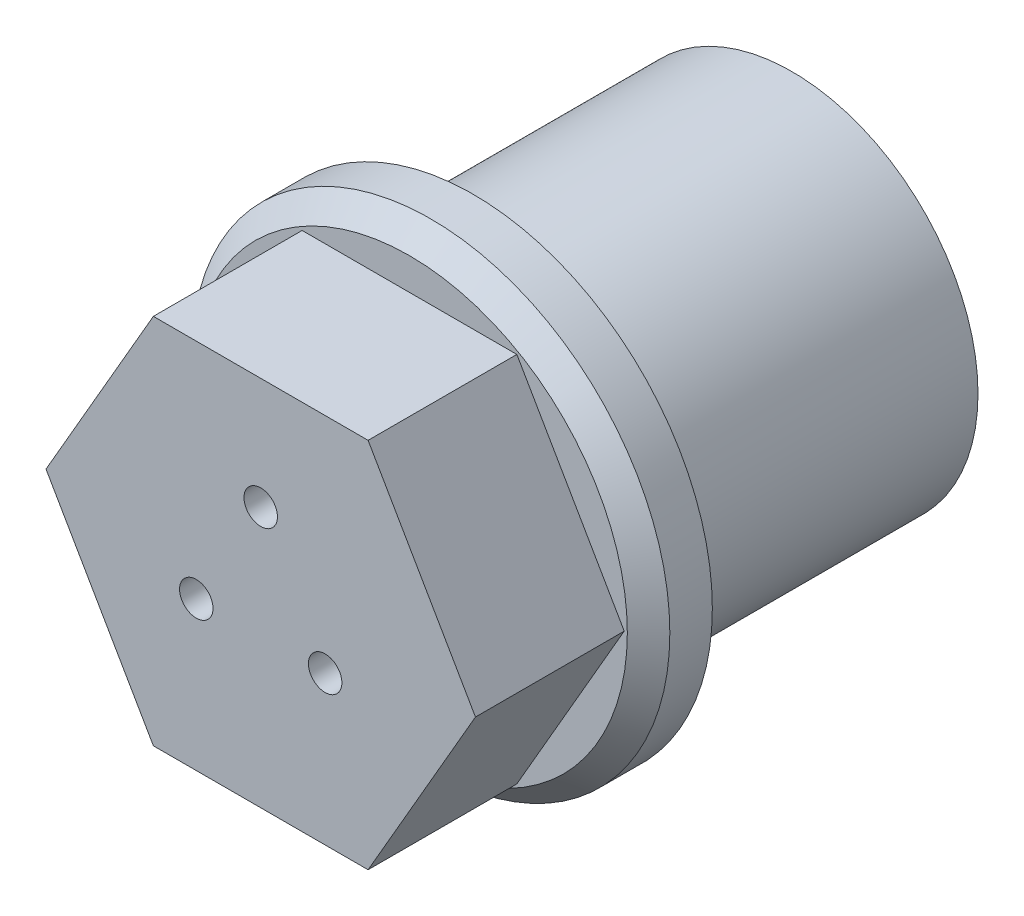
SolidWorks part; units mm, degrees
ref_plane "Front" through (0, 0, 0) normal (0, 0, 1) x (1, 0, 0)
ref_plane "Top" through (0, 0, 0) normal (0, 1, 0) x (1, 0, 0)
ref_plane "Right" through (0, 0, 0) normal (1, 0, 0) x (0, 0, -1)
sketch "Sketch1" plane through (0, 0, 0) normal (0, 0, 1) x (1, 0, 0)
  circle A0 centre (0, 0) radius 11.1125
  dimension "D1" = 22.225
extrude "Boss-Extrude1" add sketch "Sketch1" along normal blind 19.05
sketch "Sketch2" plane through (0, 0, 19.05) normal (0, 0, 1) x (1, 0, 0)
  circle A0 centre (0, 0) radius 14.2875
  dimension "D1" = 28.575
extrude "Boss-Extrude2" add sketch "Sketch2" along normal blind 12.7
sketch "Sketch3" plane through (0, 0, 31.75) normal (0, 0, 1) x (1, 0, 0)
  line L1 (12.8316, 0) -> (6.4158, 11.1125)
  line L2 (6.4158, 11.1125) -> (-6.4158, 11.1125)
  line L3 (-6.4158, 11.1125) -> (-12.8316, 0)
  line L4 (-12.8316, 0) -> (-6.4158, -11.1125)
  line L5 (-6.4158, -11.1125) -> (6.4158, -11.1125)
  line L6 (6.4158, -11.1125) -> (12.8316, 0)
  circle A0 centre (0, 0) radius 11.1125 construction
  circle A2 centre (0, 0) radius 14.2875
  circle A3 centre (0, 0) radius 14.2875
  dimension "D1" = 22.225
  dimension "D2" = 0
extrude "Cut-Extrude1" cut sketch "Sketch3" against normal blind 8.89
chamfer "Chamfer1" distance 1.27 angle 45 1 edges at (14.2875, 0, 22.86)
sketch "Sketch4" plane through (0, 0, 31.75) normal (0, 0, 1) x (1, 0, 0)
  circle A0 centre (0, 0) radius 4.445 construction
  circle A1 centre (0, 4.445) radius 1
  circle A2 centre (3.8495, -2.2225) radius 1
  circle A3 centre (-3.8495, -2.2225) radius 1
  point P11 (0, 0)
  dimension "D1" = 8.89
  dimension "D2" = 2
  dimension "D3" = 3
sketch "Sketch5" plane through (0, 0, 22.86) normal (0, 0, 1) x (1, 0, 0)
  circle A0 centre (0, 0) radius 5.445
sketch "Sketch6" plane through (0, 0, 0) normal (0, 0, -1) x (-1, 0, 0)
  circle A0 centre (0, 0) radius 9.5504
  dimension "D1" = 19.1008
loft "Cut-Loft1" cut profiles "Sketch6", "Sketch5" connector at (2.3518, 9.2563, 0) connector at (2.6441, 4.7599, 22.86)
extrude "Cut-Extrude2" cut sketch "Sketch4" against normal up to next
